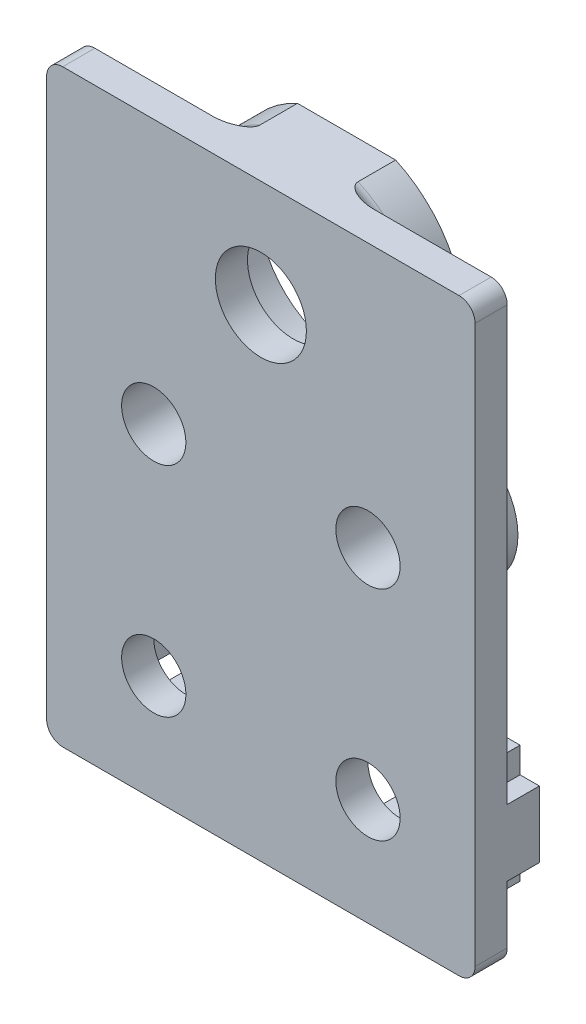
SolidWorks part; units mm, degrees
ref_plane "前视基准面" through (0, 0, 0) normal (0, 0, 1) x (1, 0, 0)
ref_plane "上视基准面" through (0, 0, 0) normal (0, 1, 0) x (1, 0, 0)
ref_plane "右视基准面" through (0, 0, 0) normal (1, 0, 0) x (0, 0, -1)
sketch "草图1" plane through (0, 0, 0) normal (0, 0, 1) x (1, 0, 0)
  line L0 (-20, 0) -> (-20, -6.9)
  line L1 (-20, 0) -> (-13.1, 0)
  line L4 (-6.9, -1.8) -> (-6.9, 0)
  line L5 (-13.1, -1.8) -> (-13.1, 0)
  line L6 (-4.5, -3.4393) -> (-4.5, -1.8)
  line L7 (-4.5, -3.4393) -> (-7.1607, -6.1)
  line L8 (-3.4393, -4.5) -> (-6.1, -7.1607)
  line L9 (-16.5607, -4.5) -> (-18.2, -4.5)
  line L10 (-13.1, -1.8) -> (-15.5, -1.8)
  line L11 (-6.9, 0) -> (0, 0)
  line L12 (-12.8393, -13.9) -> (-7.1607, -13.9)
  line L13 (-13.9, -12.8393) -> (-13.9, -7.1607)
  line L14 (-12.8393, -6.1) -> (-7.1607, -6.1)
  line L15 (-6.1, -12.8393) -> (-6.1, -7.1607)
  line L16 (-10, -6.1) -> (-10, -13.9) construction
  line L17 (-13.9, -10) -> (-6.1, -10) construction
  line L18 (-6.9, -1.8) -> (-4.5, -1.8)
  line L19 (-16.5607, -4.5) -> (-13.9, -7.1607)
  line L20 (-15.5, -3.4393) -> (-12.8393, -6.1)
  line L21 (-15.5, -3.4393) -> (-15.5, -1.8)
  line L22 (-18.2, -6.9) -> (-18.2, -4.5)
  line L23 (-18.2, -6.9) -> (-20, -6.9)
  line L24 (-18.2, -13.1) -> (-20, -13.1)
  line L25 (-18.2, -13.1) -> (-18.2, -15.5)
  line L26 (-15.5, -16.5607) -> (-15.5, -18.2)
  line L27 (-15.5, -16.5607) -> (-12.8393, -13.9)
  line L28 (-16.5607, -15.5) -> (-13.9, -12.8393)
  line L29 (-6.9, -18.2) -> (-4.5, -18.2)
  line L30 (-6.9, -20) -> (0, -20)
  line L31 (-13.1, -18.2) -> (-15.5, -18.2)
  line L32 (-16.5607, -15.5) -> (-18.2, -15.5)
  line L33 (-3.4393, -15.5) -> (-6.1, -12.8393)
  line L34 (-4.5, -16.5607) -> (-7.1607, -13.9)
  line L35 (-4.5, -16.5607) -> (-4.5, -18.2)
  line L36 (-13.1, -18.2) -> (-13.1, -20)
  line L37 (-6.9, -18.2) -> (-6.9, -20)
  line L38 (-20, -20) -> (-13.1, -20)
  line L39 (-20, -20) -> (-20, -13.1)
  line L40 (0, 0) -> (6.9, 0)
  line L41 (18.2, -6.9) -> (20, -6.9)
  line L42 (13.1, -1.8) -> (13.1, 0)
  line L43 (6.9, -1.8) -> (6.9, 0)
  line L44 (20, 0) -> (20, -6.9)
  line L45 (18.2, -6.9) -> (18.2, -4.5)
  line L46 (15.5, -3.4393) -> (15.5, -1.8)
  line L47 (15.5, -3.4393) -> (12.8393, -6.1)
  line L48 (16.5607, -4.5) -> (13.9, -7.1607)
  line L49 (6.9, -1.8) -> (4.5, -1.8)
  line L50 (13.1, 0) -> (20, 0)
  line L51 (7.1607, -13.9) -> (12.8393, -13.9)
  line L52 (6.1, -12.8393) -> (6.1, -7.1607)
  line L53 (7.1607, -6.1) -> (12.8393, -6.1)
  line L54 (13.9, -12.8393) -> (13.9, -7.1607)
  line L55 (13.1, -1.8) -> (15.5, -1.8)
  line L56 (16.5607, -4.5) -> (18.2, -4.5)
  line L57 (3.4393, -4.5) -> (6.1, -7.1607)
  line L58 (4.5, -3.4393) -> (7.1607, -6.1)
  line L59 (4.5, -3.4393) -> (4.5, -1.8)
  line L60 (4.5, -16.5607) -> (4.5, -18.2)
  line L61 (4.5, -16.5607) -> (7.1607, -13.9)
  line L62 (3.4393, -15.5) -> (6.1, -12.8393)
  line L63 (16.5607, -15.5) -> (18.2, -15.5)
  line L64 (13.1, -18.2) -> (15.5, -18.2)
  line L65 (13.1, -20) -> (20, -20)
  line L66 (6.9, -18.2) -> (4.5, -18.2)
  line L67 (16.5607, -15.5) -> (13.9, -12.8393)
  line L68 (15.5, -16.5607) -> (12.8393, -13.9)
  line L69 (15.5, -16.5607) -> (15.5, -18.2)
  line L70 (18.2, -13.1) -> (18.2, -15.5)
  line L71 (20, -20) -> (20, -13.1)
  line L72 (6.9, -18.2) -> (6.9, -20)
  line L73 (13.1, -18.2) -> (13.1, -20)
  line L74 (18.2, -13.1) -> (20, -13.1)
  line L75 (0, -20) -> (6.9, -20)
  line L78 (10, -6.1) -> (10, -13.9) construction
  line L79 (6.1, -10) -> (13.9, -10) construction
  line L80 (3.4393, -1.8) -> (-3.4393, -1.8)
  line L81 (-3.4393, -1.8) -> (-3.4393, -4.5)
  line L82 (3.4393, -1.8) -> (3.4393, -4.5)
  line L83 (-3.4393, -18.2) -> (-3.4393, -15.5)
  line L84 (3.4393, -18.2) -> (3.4393, -15.5)
  line L85 (3.4393, -18.2) -> (-3.4393, -18.2)
  circle A0 centre (-10, -10) radius 2.55
  circle A1 centre (10, -10) radius 2.55
  point P0 (-10, -10)
  point P8 (-10, -1.8)
  point P9 (-9.8043, -1.8)
  point P13 (-10, -1.8)
  point P20 (-5, -5)
  point P33 (-15, -5)
  point P50 (-15, -15)
  point P51 (-5, -15)
  point P52 (-10, -18.2)
  point P53 (-9.8043, -18.2)
  point P54 (10, -10)
  point P58 (10, -1.8)
  point P59 (10.1957, -1.8)
  point P63 (10, -1.8)
  point P70 (15, -5)
  point P83 (5, -5)
  point P102 (5, -15)
  point P103 (15, -15)
  point P104 (10, -18.2)
  point P105 (10.1957, -18.2)
extrude "凸台-拉伸1" add sketch "草图1" along normal blind 10
sketch "草图2" plane through (0, 0, 10) normal (0, 0, 1) x (1, 0, 0)
  line L1 (-20, 0) -> (20, 0)
  line L2 (-20, 0) -> (-20, -20)
  line L3 (-20, -20) -> (20, -20)
  line L4 (20, 0) -> (20, -20)
extrude "凸台-拉伸2" add sketch "草图2" along normal blind 3
sketch "草图3" plane through (0, 0, 10) normal (0, 0, -1) x (-1, 0, 0)
  line L0 (-13.1, -20) -> (-6.9, -20) construction
  line L1 (-6.9, -20) -> (-6.9, -18.2) construction
  line L2 (-6.9, -18.2) -> (-4.5, -18.2) construction
  line L3 (-4.5, -18.2) -> (-4.5, -16.5607) construction
  line L4 (-4.5, -16.5607) -> (-7.1607, -13.9) construction
  line L5 (-7.1607, -13.9) -> (-12.8393, -13.9) construction
  line L6 (-12.8393, -13.9) -> (-15.5, -16.5607) construction
  line L7 (-15.5, -16.5607) -> (-15.5, -18.2) construction
  line L8 (-15.5, -18.2) -> (-13.1, -18.2) construction
  line L9 (-13.1, -18.2) -> (-13.1, -20) construction
  line L10 (-20, -6.9) -> (-20, -13.1) construction
  line L11 (-20, -13.1) -> (-18.2, -13.1) construction
  line L12 (-18.2, -13.1) -> (-18.2, -15.5) construction
  line L13 (-18.2, -15.5) -> (-16.5607, -15.5) construction
  line L14 (-16.5607, -15.5) -> (-13.9, -12.8393) construction
  line L15 (-13.9, -12.8393) -> (-13.9, -7.1607) construction
  line L16 (-13.9, -7.1607) -> (-16.5607, -4.5) construction
  line L17 (-16.5607, -4.5) -> (-18.2, -4.5) construction
  line L18 (-18.2, -4.5) -> (-18.2, -6.9) construction
  line L19 (-18.2, -6.9) -> (-20, -6.9) construction
  line L20 (-6.9, 0) -> (-13.1, 0) construction
  line L21 (-13.1, 0) -> (-13.1, -1.8) construction
  line L22 (-13.1, -1.8) -> (-15.5, -1.8) construction
  line L23 (-15.5, -1.8) -> (-15.5, -3.4393) construction
  line L24 (-15.5, -3.4393) -> (-12.8393, -6.1) construction
  line L25 (-12.8393, -6.1) -> (-7.1607, -6.1) construction
  line L26 (-7.1607, -6.1) -> (-4.5, -3.4393) construction
  line L27 (-4.5, -3.4393) -> (-4.5, -1.8) construction
  line L28 (-4.5, -1.8) -> (-6.9, -1.8) construction
  line L29 (-6.9, -1.8) -> (-6.9, 0) construction
  line L30 (6.9, -20) -> (13.1, -20) construction
  line L31 (13.1, -20) -> (13.1, -18.2) construction
  line L32 (13.1, -18.2) -> (15.5, -18.2) construction
  line L33 (15.5, -18.2) -> (15.5, -16.5607) construction
  line L34 (15.5, -16.5607) -> (12.8393, -13.9) construction
  line L35 (12.8393, -13.9) -> (7.1607, -13.9) construction
  line L36 (7.1607, -13.9) -> (4.5, -16.5607) construction
  line L37 (4.5, -16.5607) -> (4.5, -18.2) construction
  line L38 (4.5, -18.2) -> (6.9, -18.2) construction
  line L39 (6.9, -18.2) -> (6.9, -20) construction
  line L40 (20, -13.1) -> (20, -6.9) construction
  line L41 (20, -6.9) -> (18.2, -6.9) construction
  line L42 (18.2, -6.9) -> (18.2, -4.5) construction
  line L43 (18.2, -4.5) -> (16.5607, -4.5) construction
  line L44 (16.5607, -4.5) -> (13.9, -7.1607) construction
  line L45 (13.9, -7.1607) -> (13.9, -12.8393) construction
  line L46 (13.9, -12.8393) -> (16.5607, -15.5) construction
  line L47 (16.5607, -15.5) -> (18.2, -15.5) construction
  line L48 (18.2, -15.5) -> (18.2, -13.1) construction
  line L49 (18.2, -13.1) -> (20, -13.1) construction
  line L50 (13.1, 0) -> (6.9, 0) construction
  line L51 (6.9, 0) -> (6.9, -1.8) construction
  line L52 (6.9, -1.8) -> (4.5, -1.8) construction
  line L53 (4.5, -1.8) -> (4.5, -3.4393) construction
  line L54 (4.5, -3.4393) -> (7.1607, -6.1) construction
  line L55 (7.1607, -6.1) -> (12.8393, -6.1) construction
  line L56 (12.8393, -6.1) -> (15.5, -3.4393) construction
  line L57 (15.5, -3.4393) -> (15.5, -1.8) construction
  line L58 (15.5, -1.8) -> (13.1, -1.8) construction
  line L59 (13.1, -1.8) -> (13.1, 0) construction
  line L60 (-13.1, -20) -> (-6.9, -20)
  line L61 (-6.9, -20) -> (-6.9, -18.2)
  line L62 (-6.9, -18.2) -> (-4.5, -18.2)
  line L63 (-4.5, -18.2) -> (-4.5, -16.5607)
  line L64 (-4.5, -16.5607) -> (-7.1607, -13.9)
  line L65 (-7.1607, -13.9) -> (-12.8393, -13.9)
  line L66 (-12.8393, -13.9) -> (-15.5, -16.5607)
  line L67 (-15.5, -16.5607) -> (-15.5, -18.2)
  line L68 (-15.5, -18.2) -> (-13.1, -18.2)
  line L69 (-13.1, -18.2) -> (-13.1, -20)
  line L70 (-20, -6.9) -> (-20, -13.1)
  line L71 (-20, -13.1) -> (-18.2, -13.1)
  line L72 (-18.2, -13.1) -> (-18.2, -15.5)
  line L73 (-18.2, -15.5) -> (-16.5607, -15.5)
  line L74 (-16.5607, -15.5) -> (-13.9, -12.8393)
  line L75 (-13.9, -12.8393) -> (-13.9, -7.1607)
  line L76 (-13.9, -7.1607) -> (-16.5607, -4.5)
  line L77 (-16.5607, -4.5) -> (-18.2, -4.5)
  line L78 (-18.2, -4.5) -> (-18.2, -6.9)
  line L79 (-18.2, -6.9) -> (-20, -6.9)
  line L80 (-6.9, 0) -> (-13.1, 0)
  line L81 (-13.1, 0) -> (-13.1, -1.8)
  line L82 (-13.1, -1.8) -> (-15.5, -1.8)
  line L83 (-15.5, -1.8) -> (-15.5, -3.4393)
  line L84 (-15.5, -3.4393) -> (-12.8393, -6.1)
  line L85 (-12.8393, -6.1) -> (-7.1607, -6.1)
  line L86 (-7.1607, -6.1) -> (-4.5, -3.4393)
  line L87 (-4.5, -3.4393) -> (-4.5, -1.8)
  line L88 (-4.5, -1.8) -> (-6.9, -1.8)
  line L89 (-6.9, -1.8) -> (-6.9, 0)
  line L90 (6.9, -20) -> (13.1, -20)
  line L91 (13.1, -20) -> (13.1, -18.2)
  line L92 (13.1, -18.2) -> (15.5, -18.2)
  line L93 (15.5, -18.2) -> (15.5, -16.5607)
  line L94 (15.5, -16.5607) -> (12.8393, -13.9)
  line L95 (12.8393, -13.9) -> (7.1607, -13.9)
  line L96 (7.1607, -13.9) -> (4.5, -16.5607)
  line L97 (4.5, -16.5607) -> (4.5, -18.2)
  line L98 (4.5, -18.2) -> (6.9, -18.2)
  line L99 (6.9, -18.2) -> (6.9, -20)
  line L100 (20, -13.1) -> (20, -6.9)
  line L101 (20, -6.9) -> (18.2, -6.9)
  line L102 (18.2, -6.9) -> (18.2, -4.5)
  line L103 (18.2, -4.5) -> (16.5607, -4.5)
  line L104 (16.5607, -4.5) -> (13.9, -7.1607)
  line L105 (13.9, -7.1607) -> (13.9, -12.8393)
  line L106 (13.9, -12.8393) -> (16.5607, -15.5)
  line L107 (16.5607, -15.5) -> (18.2, -15.5)
  line L108 (18.2, -15.5) -> (18.2, -13.1)
  line L109 (18.2, -13.1) -> (20, -13.1)
  line L110 (13.1, 0) -> (6.9, 0)
  line L111 (6.9, 0) -> (6.9, -1.8)
  line L112 (6.9, -1.8) -> (4.5, -1.8)
  line L113 (4.5, -1.8) -> (4.5, -3.4393)
  line L114 (4.5, -3.4393) -> (7.1607, -6.1)
  line L115 (7.1607, -6.1) -> (12.8393, -6.1)
  line L116 (12.8393, -6.1) -> (15.5, -3.4393)
  line L117 (15.5, -3.4393) -> (15.5, -1.8)
  line L118 (15.5, -1.8) -> (13.1, -1.8)
  line L119 (13.1, -1.8) -> (13.1, 0)
extrude "凸台-拉伸3" add sketch "草图3" along normal blind 3
sketch "草图4" plane through (0, 0, 0) normal (0, 0, -1) x (-1, 0, 0)
  line L64 (6.9, 0) -> (-6.9, 0)
  line L65 (-6.9, 0) -> (-6.9, -1.8)
  line L66 (-6.9, -1.8) -> (-4.5, -1.8)
  line L67 (-4.5, -1.8) -> (-4.5, -3.4393)
  line L68 (-4.5, -3.4393) -> (-7.1607, -6.1)
  line L69 (-7.1607, -6.1) -> (-12.8393, -6.1)
  line L70 (-12.8393, -6.1) -> (-15.5, -3.4393)
  line L71 (-15.5, -3.4393) -> (-15.5, -1.8)
  line L72 (-15.5, -1.8) -> (-13.1, -1.8)
  line L73 (-13.1, -1.8) -> (-13.1, 0)
  line L74 (-13.1, 0) -> (-20, 0)
  line L75 (-20, 0) -> (-20, -6.9)
  line L76 (-20, -6.9) -> (-18.2, -6.9)
  line L77 (-18.2, -6.9) -> (-18.2, -4.5)
  line L78 (-18.2, -4.5) -> (-16.5607, -4.5)
  line L79 (-16.5607, -4.5) -> (-13.9, -7.1607)
  line L80 (-13.9, -7.1607) -> (-13.9, -12.8393)
  line L81 (-13.9, -12.8393) -> (-16.5607, -15.5)
  line L82 (-16.5607, -15.5) -> (-18.2, -15.5)
  line L83 (-18.2, -15.5) -> (-18.2, -13.1)
  line L84 (-18.2, -13.1) -> (-20, -13.1)
  line L85 (-20, -13.1) -> (-20, -20)
  line L86 (-20, -20) -> (-13.1, -20)
  line L87 (-13.1, -20) -> (-13.1, -18.2)
  line L88 (-13.1, -18.2) -> (-15.5, -18.2)
  line L89 (-15.5, -18.2) -> (-15.5, -16.5607)
  line L90 (-15.5, -16.5607) -> (-12.8393, -13.9)
  line L91 (-12.8393, -13.9) -> (-7.1607, -13.9)
  line L92 (-7.1607, -13.9) -> (-4.5, -16.5607)
  line L93 (-4.5, -16.5607) -> (-4.5, -18.2)
  line L94 (-4.5, -18.2) -> (-6.9, -18.2)
  line L95 (-6.9, -18.2) -> (-6.9, -20)
  line L96 (-6.9, -20) -> (6.9, -20)
  line L97 (6.9, -20) -> (6.9, -18.2)
  line L98 (6.9, -18.2) -> (4.5, -18.2)
  line L99 (4.5, -18.2) -> (4.5, -16.5607)
  line L100 (4.5, -16.5607) -> (7.1607, -13.9)
  line L101 (7.1607, -13.9) -> (12.8393, -13.9)
  line L102 (12.8393, -13.9) -> (15.5, -16.5607)
  line L103 (15.5, -16.5607) -> (15.5, -18.2)
  line L104 (15.5, -18.2) -> (13.1, -18.2)
  line L105 (13.1, -18.2) -> (13.1, -20)
  line L106 (13.1, -20) -> (20, -20)
  line L107 (20, -20) -> (20, -13.1)
  line L108 (20, -13.1) -> (18.2, -13.1)
  line L109 (18.2, -13.1) -> (18.2, -15.5)
  line L110 (18.2, -15.5) -> (16.5607, -15.5)
  line L111 (16.5607, -15.5) -> (13.9, -12.8393)
  line L112 (13.9, -12.8393) -> (13.9, -7.1607)
  line L113 (13.9, -7.1607) -> (16.5607, -4.5)
  line L114 (16.5607, -4.5) -> (18.2, -4.5)
  line L115 (18.2, -4.5) -> (18.2, -6.9)
  line L116 (18.2, -6.9) -> (20, -6.9)
  line L117 (20, -6.9) -> (20, 0)
  line L118 (20, 0) -> (13.1, 0)
  line L119 (13.1, 0) -> (13.1, -1.8)
  line L120 (13.1, -1.8) -> (15.5, -1.8)
  line L121 (15.5, -1.8) -> (15.5, -3.4393)
  line L122 (15.5, -3.4393) -> (12.8393, -6.1)
  line L123 (12.8393, -6.1) -> (7.1607, -6.1)
  line L124 (7.1607, -6.1) -> (4.5, -3.4393)
  line L125 (4.5, -3.4393) -> (4.5, -1.8)
  line L126 (4.5, -1.8) -> (6.9, -1.8)
  line L127 (6.9, -1.8) -> (6.9, 0)
  line L128 (6.9, 0) -> (-6.9, 0)
  line L129 (-6.9, 0) -> (-6.9, -1.8)
  line L130 (-6.9, -1.8) -> (-4.5, -1.8)
  line L131 (-4.5, -1.8) -> (-4.5, -3.4393)
  line L132 (-4.5, -3.4393) -> (-7.1607, -6.1)
  line L133 (-7.1607, -6.1) -> (-12.8393, -6.1)
  line L134 (-12.8393, -6.1) -> (-15.5, -3.4393)
  line L135 (-15.5, -3.4393) -> (-15.5, -1.8)
  line L136 (-15.5, -1.8) -> (-13.1, -1.8)
  line L137 (-13.1, -1.8) -> (-13.1, 0)
  line L138 (-13.1, 0) -> (-20, 0)
  line L139 (-20, 0) -> (-20, -6.9)
  line L140 (-20, -6.9) -> (-18.2, -6.9)
  line L141 (-18.2, -6.9) -> (-18.2, -4.5)
  line L142 (-18.2, -4.5) -> (-16.5607, -4.5)
  line L143 (-16.5607, -4.5) -> (-13.9, -7.1607)
  line L144 (-13.9, -7.1607) -> (-13.9, -12.8393)
  line L145 (-13.9, -12.8393) -> (-16.5607, -15.5)
  line L146 (-16.5607, -15.5) -> (-18.2, -15.5)
  line L147 (-18.2, -15.5) -> (-18.2, -13.1)
  line L148 (-18.2, -13.1) -> (-20, -13.1)
  line L149 (-20, -13.1) -> (-20, -20)
  line L150 (-20, -20) -> (-13.1, -20)
  line L151 (-13.1, -20) -> (-13.1, -18.2)
  line L152 (-13.1, -18.2) -> (-15.5, -18.2)
  line L153 (-15.5, -18.2) -> (-15.5, -16.5607)
  line L154 (-15.5, -16.5607) -> (-12.8393, -13.9)
  line L155 (-12.8393, -13.9) -> (-7.1607, -13.9)
  line L156 (-7.1607, -13.9) -> (-4.5, -16.5607)
  line L157 (-4.5, -16.5607) -> (-4.5, -18.2)
  line L158 (-4.5, -18.2) -> (-6.9, -18.2)
  line L159 (-6.9, -18.2) -> (-6.9, -20)
  line L160 (-6.9, -20) -> (6.9, -20)
  line L161 (6.9, -20) -> (6.9, -18.2)
  line L162 (6.9, -18.2) -> (4.5, -18.2)
  line L163 (4.5, -18.2) -> (4.5, -16.5607)
  line L164 (4.5, -16.5607) -> (7.1607, -13.9)
  line L165 (7.1607, -13.9) -> (12.8393, -13.9)
  line L166 (12.8393, -13.9) -> (15.5, -16.5607)
  line L167 (15.5, -16.5607) -> (15.5, -18.2)
  line L168 (15.5, -18.2) -> (13.1, -18.2)
  line L169 (13.1, -18.2) -> (13.1, -20)
  line L170 (13.1, -20) -> (20, -20)
  line L171 (20, -20) -> (20, -13.1)
  line L172 (20, -13.1) -> (18.2, -13.1)
  line L173 (18.2, -13.1) -> (18.2, -15.5)
  line L174 (18.2, -15.5) -> (16.5607, -15.5)
  line L175 (16.5607, -15.5) -> (13.9, -12.8393)
  line L176 (13.9, -12.8393) -> (13.9, -7.1607)
  line L177 (13.9, -7.1607) -> (16.5607, -4.5)
  line L178 (16.5607, -4.5) -> (18.2, -4.5)
  line L179 (18.2, -4.5) -> (18.2, -6.9)
  line L180 (18.2, -6.9) -> (20, -6.9)
  line L181 (20, -6.9) -> (20, 0)
  line L182 (20, 0) -> (13.1, 0)
  line L183 (13.1, 0) -> (13.1, -1.8)
  line L184 (13.1, -1.8) -> (15.5, -1.8)
  line L185 (15.5, -1.8) -> (15.5, -3.4393)
  line L186 (15.5, -3.4393) -> (12.8393, -6.1)
  line L187 (12.8393, -6.1) -> (7.1607, -6.1)
  line L188 (7.1607, -6.1) -> (4.5, -3.4393)
  line L189 (4.5, -3.4393) -> (4.5, -1.8)
  line L190 (4.5, -1.8) -> (6.9, -1.8)
  line L191 (6.9, -1.8) -> (6.9, 0)
  dimension "D1" = 0
extrude "切除-拉伸1" cut sketch "草图4" against normal blind 10
sketch "草图5" plane through (0, 0, 10) normal (0, 0, -1) x (-1, 0, 0)
  circle A0 centre (-10, -10) radius 3
  circle A1 centre (10, -10) radius 3
extrude "切除-拉伸2" cut sketch "草图5" against normal blind 10
sketch "草图6" plane through (0, 0, 13) normal (0, 0, 1) x (1, 0, 0)
  line L0 (-20, 0) -> (20, 0)
  line L1 (0, 35) -> (-20, 35)
  line L2 (-20, 35) -> (-20, 0)
  line L3 (20, 0) -> (20, 35)
  line L4 (0, 35) -> (20, 35)
  circle A0 centre (-10, 10.36) radius 3
  circle A1 centre (10, 10.36) radius 3
  circle A2 centre (0, 25) radius 4.25
extrude "凸台-拉伸4" add sketch "草图6" against normal blind 3
fillet "圆角1" radius 1.5 4 edges at (-20, -20, 11.5) (-20, 35, 11.5) (20, -20, 11.5) (20, 35, 11.5)
sketch "草图7" plane through (0, 0, 10) normal (0, 0, -1) x (-1, 0, 0)
  circle A1 centre (10, 10.36) radius 3 construction
  circle A2 centre (-10, 10.36) radius 3 construction
  circle A4 centre (10, 10.36) radius 3
  circle A5 centre (-10, 10.36) radius 3
  circle A6 centre (-10, 10.36) radius 6
  circle A7 centre (10, 10.36) radius 6
  dimension "D1" = 3
extrude "凸台-拉伸5" add sketch "草图7" along normal blind 5
sketch "草图8" plane through (0, 0, 10) normal (0, 0, -1) x (-1, 0, 0)
  line L0 (-4.5826, 35) -> (4.5826, 35)
  line L1 (-18.5, 35) -> (18.5, 35) construction
  circle A0 centre (0, 25) radius 8.25
  arc A1 (-4.5826, 35) -> (4.5826, 35) centre (0, 25) ccw
extrude "凸台-拉伸6" add sketch "草图8" along normal blind 5
fillet "圆角3" radius 1.5 3 edges at (-4, 10.36, 10) (16, 10.36, 10) (0, 14, 10)
